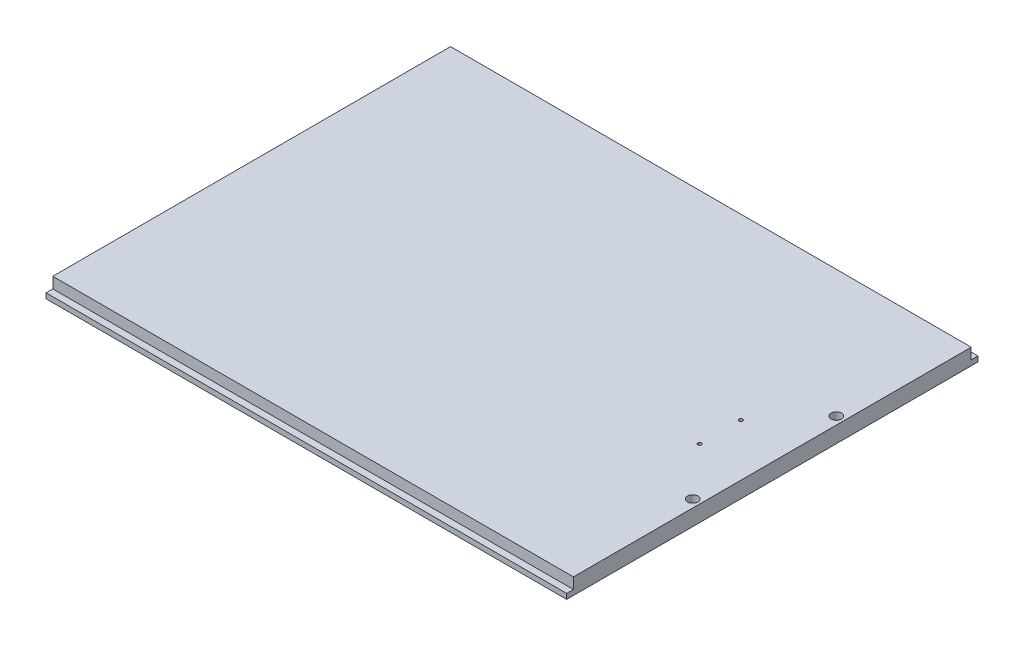
SolidWorks part; units mm, degrees
ref_plane "前视基准面" through (0, 0, 0) normal (0, 0, 1) x (1, 0, 0)
ref_plane "上视基准面" through (0, 0, 0) normal (0, 1, 0) x (1, 0, 0)
ref_plane "右视基准面" through (0, 0, 0) normal (1, 0, 0) x (0, 0, -1)
other "Configuration Table"
sketch "草图1" plane through (0, 0, 0) normal (1, 0, 0) x (0, 0, -1)
  line L1 (-38.2, 0) -> (38.2, 0)
  line L2 (-38.2, 0) -> (-38.2, -2.1)
  line L3 (-38.2, -2.1) -> (38.2, -2.1)
  line L4 (38.2, 0) -> (38.2, -2.1)
  line L5 (-39.5, -2.1) -> (39.5, -2.1)
  line L6 (-39.5, -2.1) -> (-39.5, -3.1)
  line L7 (-39.5, -3.1) -> (39.5, -3.1)
  line L8 (39.5, -2.1) -> (39.5, -3.1)
  dimension "D1" = 1
  dimension "D2" = 2.1
  dimension "D3" = 76.4
  dimension "D4" = 1.3
  dimension "D5" = 1.3
extrude "凸台-拉伸1" add sketch "草图1" along normal blind 100 contours L2 L3 L4 L1 | L5 L8 L7 L6
sketch "草图2" plane through (0, 0, 0) normal (-1, 0, 0) x (0, 0, 1)
  circle A0 centre (-13.8, -1.5) radius 0.35
  circle A1 centre (13.8, -1.5) radius 0.35
  dimension "D1" = 0.7
extrude "切除-拉伸1" cut sketch "草图2" against normal blind 3
sketch "草图4" plane through (0, 0, 0) normal (0, 1, 0) x (1, 0, 0)
  circle A0 centre (98.5, -13.8) radius 0.6
  circle A1 centre (98.5, -13.8) radius 1
  circle A2 centre (98.5, 13.8) radius 0.6
  circle A3 centre (98.5, 13.8) radius 1
  dimension "D1" = 1.2
  dimension "D2" = 2
extrude "切除-拉伸2" cut sketch "草图4" against normal through all contours A2 | A0
extrude "切除-拉伸3" cut sketch "草图4<3>" against normal blind 1.5 contours A1 | A3
sketch "草图4<3>" plane through (0, 0, 0) normal (0, 1, 0) x (1, 0, 0) same geometry as "草图4"
sketch "草图5" plane through (0, 0, 0) normal (0, 1, 0) x (1, 0, 0)
  line L0 (90, 38.2) -> (90, 3.95) construction
  line L1 (100, -38.2) -> (100, 38.2) construction
  line L2 (90, -3.95) -> (90, -38.2) construction
  line L3 (100, -38.2) -> (0, -38.2) construction
  line L4 (100, 38.2) -> (0, 38.2) construction
  circle A0 centre (90, 3.95) radius 0.35
  circle A1 centre (90, -3.95) radius 0.35
  dimension "D2" = 0.7
  dimension "D1" = 7.9
  dimension "D3" = 10
extrude "切除-拉伸4" cut sketch "草图5" against normal through all
